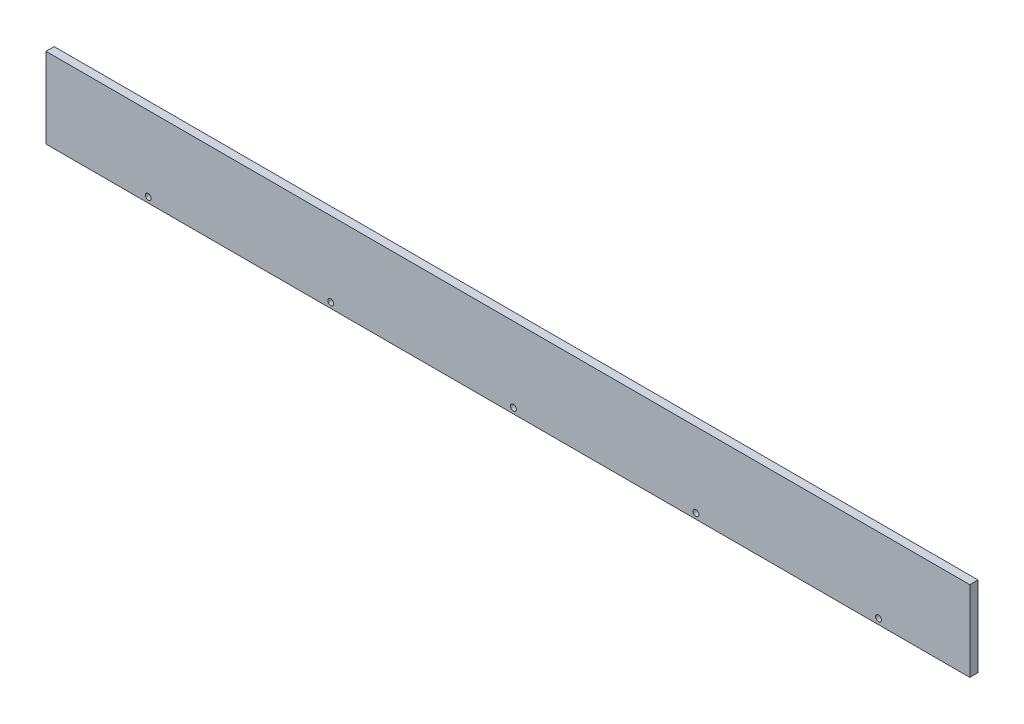
SolidWorks part; units mm, degrees
ref_plane "Front Plane" through (0, 0, 0) normal (0, 0, 1) x (1, 0, 0)
ref_plane "Top Plane" through (0, 0, 0) normal (0, 1, 0) x (1, 0, 0)
ref_plane "Right Plane" through (0, 0, 0) normal (1, 0, 0) x (0, 0, -1)
sketch "Sketch1" plane through (0, 0, 0) normal (0, 0, 1) x (1, 0, 0)
  line L1 (-253, -22) -> (253, -22)
  line L2 (-253, -22) -> (-253, 22)
  line L3 (-253, 22) -> (253, 22)
  line L4 (253, -22) -> (253, 22)
  line L5 (-253, -22) -> (253, 22) construction
  line L6 (-253, 22) -> (253, -22) construction
  circle A10 centre (203, -19) radius 1.6 construction
  circle A11 centre (103, -19) radius 1.6 construction
  circle A12 centre (3, -19) radius 1.6 construction
  circle A13 centre (-97, -19) radius 1.6 construction
  circle A14 centre (-197, -19) radius 1.6 construction
  circle A15 centre (203, -19) radius 1.6
  circle A16 centre (103, -19) radius 1.6
  circle A17 centre (3, -19) radius 1.6
  circle A18 centre (-97, -19) radius 1.6
  circle A19 centre (-197, -19) radius 1.6
  point P0 (0, 0)
  dimension "D1" = 506
  dimension "D2" = 44
extrude "Boss-Extrude1" add sketch "Sketch1" along normal blind 4.5
